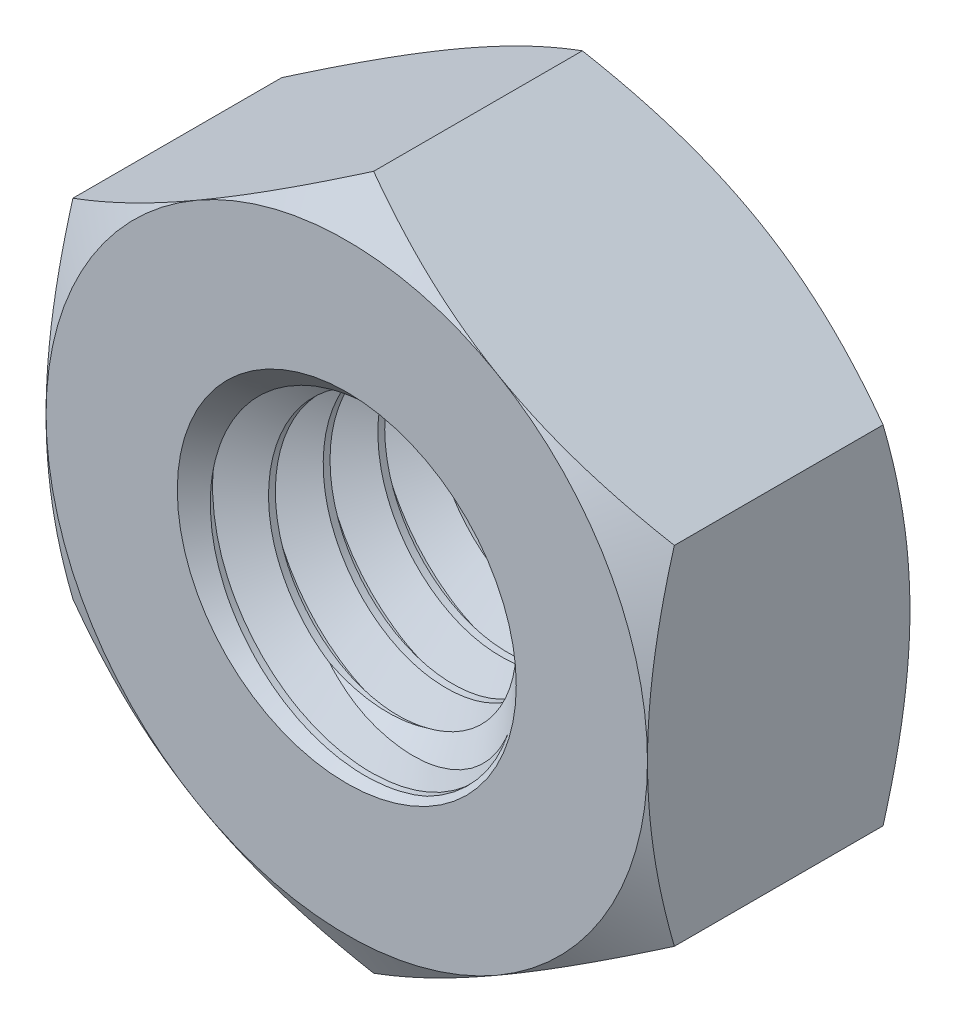
SolidWorks part; units mm, degrees
note: '?' marks a value the reader was unsure of.
ref_plane "Front" through (0, 0, 0) normal (0, 0, 1) x (1, 0, 0)
ref_plane "Top" through (0, 0, 0) normal (0, 1, 0) x (1, 0, 0)
ref_plane "Right" through (0, 0, 0) normal (1, 0, 0) x (0, 0, -1)
sketch "Sketch1" plane through (0, 0, 0) normal (0, 0, 1) x (1, 0, 0)
  line L1 (-2.75, 1.5877) -> (-2.75, -1.5877)
  line L2 (-2.75, -1.5877) -> (0, -3.1754)
  line L3 (0, -3.1754) -> (2.75, -1.5877)
  line L4 (2.75, -1.5877) -> (2.75, 1.5877)
  line L5 (2.75, 1.5877) -> (0, 3.1754)
  line L6 (0, 3.1754) -> (-2.75, 1.5877)
  circle A0 centre (0, 0) radius 2.75 construction
  circle A1 centre (0, 0) radius 1.5 construction
  point P10 (0, 1.5)
  dimension "hex" = 5.5
  dimension "dia" = 3
extrude "Extrude1" add sketch "Sketch1" along normal mid plane 2.4
sketch "Sketch4" plane through (0, 0, -1.2) normal (0, 0, -1) x (-1, 0, 0)
  circle A0 centre (0, 0) radius 1.5 construction
  circle A1 centre (0, 0) radius 1.5
sketch "Sketch10" plane through (0, 0, 1.2) normal (0, 0, 1) x (1, 0, 0)
  circle A0 centre (0, 0) radius 1.5 construction
  circle A1 centre (0, 0) radius 1.5
extrude "Cut-Extrude2" cut sketch "Sketch10" against normal through all draft 45
sketch "Sketch11" plane through (0, 0, -1.2) normal (0, 0, -1) x (-1, 0, 0)
  circle A0 centre (0, 0) radius 1.5 construction
  circle A1 centre (0, 0) radius 1.5
extrude "Cut-Extrude3" cut sketch "Sketch11" against normal through all draft 45
sketch "Sketch13" plane through (0, 0, -1.2) normal (0, 0, -1) x (-1, 0, 0)
  circle A0 centre (0, 0) radius 1.5 construction
  circle A1 centre (0, 0) radius 1.5
extrude "Boss-Extrude1" add sketch "Sketch13" against normal up to vertex (2.4 mm away) separate body up to point (-2.75, 1.5877, 1.2)
combine bodies "Combine1" operation type subtract main body 116 bodies to subtract 117
sketch "Sketch7" plane through (0, 0, 1.2) normal (0, 0, 1) x (1, 0, 0)
  circle A0 centre (0, 0) radius 2.75 construction
  circle A1 centre (0, 0) radius 2.75
extrude "Extrude2" cut sketch "Sketch7" against normal blind 25.4 draft 60 flip side to cut
mirror "Mirror2" about plane through (0, 0, 0) normal (0, 0, 1) of "Extrude2"
sketch "Sketch8" plane through (0, 0, 1.2) normal (0, 0, 1) x (1, 0, 0)
  line L0 (-1.0607, 1.0607) -> (0, 0) construction
  line L1 (0, -1.4002) -> (0, 1.4002) construction
  circle A1 centre (0, 0) radius 1.5 construction
  point P0 (-1.0607, 1.0607)
  dimension "D1" = 45
sketch "Sketch14" plane through (0, 0, 1.2) normal (0, 0, 1) x (1, 0, 0)
  line L0 (0, 0) -> (-1.5, 0) construction
  circle A0 centre (0, 0) radius 1.5 construction
curve "Helix/Spiral3" pitch 0.5 height 2.9 turns 5.8
sketch "Sketch12" plane through (0, 0, 0) normal (1, 0, 0) x (0, 0, -1)
  line L0 (1.6375, 1.5) -> (1.2, 1.5)
  line L1 (1.6375, 1.5) -> (1.45, 1.1752)
  line L2 (1.45, 1.1752) -> (1.3875, 1.1752)
  line L3 (1.3875, 1.1752) -> (1.2, 1.5)
  line L4 (1.4187, 1.1752) -> (1.4187, 1.5) construction
  line L5 (1.2937, 1.3376) -> (1.5437, 1.3376) construction
  line L6 (1.2, -1.5) -> (1.2, 1.5) construction
  dimension "D1" = 60
  dimension "D2" = 0.0625
  dimension "D3" = 0.25
ref_axis "Center Axis 1" through (0, 0, -1.4732) along (0, 0, 1)?
sweep "Sweep1" add profiles "Sketch12" path "Helix/Spiral3"
sketch "Sketch15" plane through (0, 0, -1.2) normal (0, 0, -1) x (-1, 0, 0)
  circle A2 centre (0, 0) radius 1.55
  circle A3 centre (0, 0) radius 1.55
  dimension "D1" = 0.05
extrude "Cut-Extrude4" cut sketch "Sketch15" against normal through all draft 45 and the other way through all draft 45
sketch "Sketch16" plane through (0, 0, 1.2) normal (0, 0, 1) x (1, 0, 0)
  circle A1 centre (0, 0) radius 1.55
  circle A2 centre (0, 0) radius 1.55
  dimension "D1" = 0
extrude "Cut-Extrude5" cut sketch "Sketch16" against normal through all draft 45 and the other way through all draft 45
equation "\"D3@Helix/Spiral3\"=\"length@Extrude1\"+\"D4@Helix/Spiral3\""
equation "\"D2@Sketch12\" = \"D4@Helix/Spiral3\"*.125"
equation "\"D3@Sketch12\" = \"D4@Helix/Spiral3\"*.50"
equation "\"D1@Sketch15\"=\"D4@Helix/Spiral3\"*.1"
